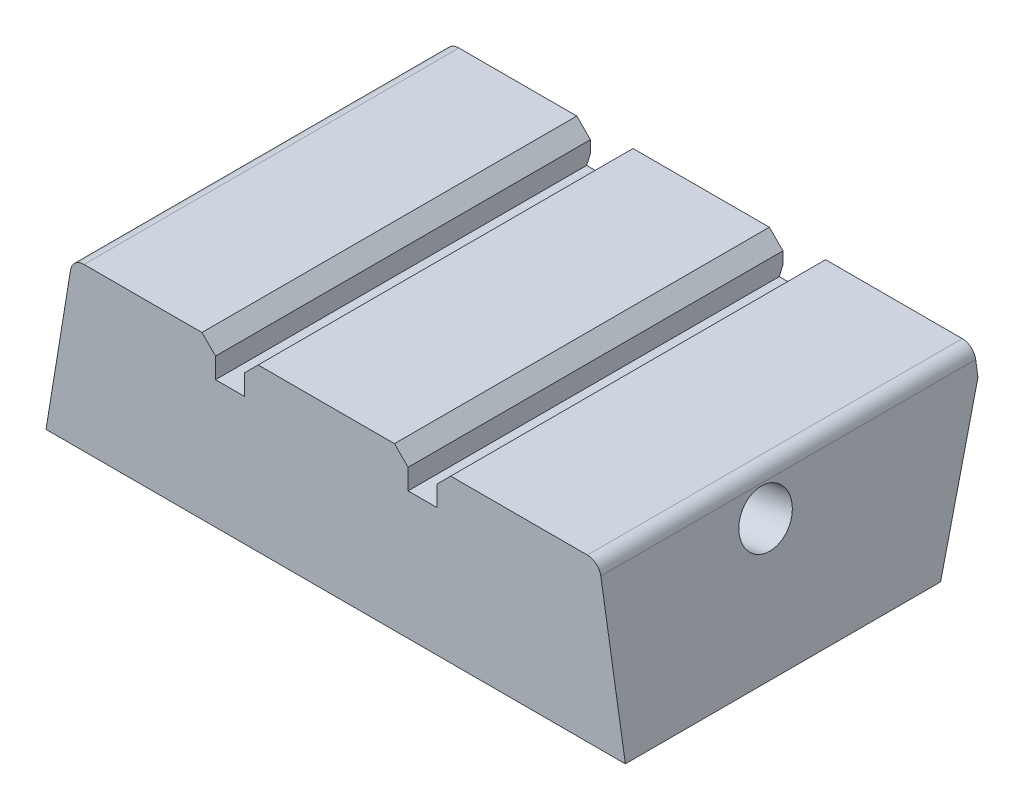
SolidWorks part; units mm, degrees
ref_plane "Front Plane" through (0, 0, 0) normal (0, 0, 1) x (1, 0, 0)
ref_plane "Top Plane" through (0, 0, 0) normal (0, 1, 0) x (1, 0, 0)
ref_plane "Right Plane" through (0, 0, 0) normal (1, 0, 0) x (0, 0, -1)
sketch "Sketch1" plane through (0, 0, 0) normal (0, 0, 1) x (1, 0, 0)
  line L0 (-17, -4.75) -> (-15.45, 4.75)
  line L1 (-17, -4.75) -> (17, -4.75)
  line L2 (-17, -4.75) -> (-17, 4.75)
  line L3 (-17, 4.75) -> (17, 4.75)
  line L4 (17, -4.75) -> (17, 4.75)
  line L5 (-17, -4.75) -> (17, 4.75) construction
  line L6 (-17, 4.75) -> (17, -4.75) construction
  line L7 (17, -4.75) -> (15.45, 4.75)
  line L8 (-7.05, 4.75) -> (-7.05, 2.75)
  line L9 (-7.05, 2.75) -> (-5.35, 2.75)
  line L10 (-5.35, 2.75) -> (-5.35, 4.75)
  line L11 (4.25, 4.75) -> (4.25, 2.75)
  line L12 (4.25, 2.75) -> (5.95, 2.75)
  line L13 (5.95, 2.75) -> (5.95, 4.75)
  point P0 (0, 0)
  dimension "D1" = 30.9
  dimension "D2" = 34
  dimension "D3" = 9.5
  dimension "D4" = 1.7
  dimension "D5" = 8.4
  dimension "D6" = 9.6
  dimension "D7" = 9.5
  dimension "D8" = 2
extrude "Boss-Extrude1" add sketch "Sketch1" along normal blind 22 contours L13 L12 L11 L3 L10 L9 L8 L0 L1 L7 region at (0.0124, -0.1619, 0)
sketch "Sketch2" plane through (0, -4.75, 0) normal (0, -1, 0) x (1, 0, 0)
  line L0 (0, 6.7) -> (0, 11.35) construction
  line L1 (-5, -6.7) -> (5, -6.7)
  line L2 (-5, -6.7) -> (-5, 6.7)
  line L3 (-5, 6.7) -> (5, 6.7)
  line L4 (5, -6.7) -> (5, 6.7)
  line L5 (-5, -6.7) -> (5, 6.7) construction
  line L6 (-5, 6.7) -> (5, -6.7) construction
  line L7 (-5.85, 11.35) -> (5.85, 11.35) construction
  line L8 (-5.85, 16) -> (5.85, 16)
  line L9 (-5.85, 6.7) -> (5.85, 6.7)
  line L10 (-17, 0) -> (17, 0) construction
  arc A0 (-5.85, 16) -> (-5.85, 6.7) centre (-5.85, 11.35) ccw
  arc A1 (5.85, 6.7) -> (5.85, 16) centre (5.85, 11.35) ccw
  point P0 (0, 0)
  point P10 (0, 11.35)
  point P17 (7.6836, 6.9018)
  line M9 (-17, 0) -> (17, 0)
  dimension "D4" = 21
  dimension "D1" = 10
  dimension "D2" = 6.7
  dimension "D3" = 16
extrude "Cut-Extrude1" cut sketch "Sketch2" against normal blind 4.6 contours L9 A1 L8 A0 L3 | L4 L3 L2 M9 region at (0, -4.75, 3.35) region at (0, -4.75, 11.35)
extrude "Cut-Extrude2" cut sketch "Sketch2<3>" against normal blind 6.5 contours L4 L3 L2 M9 region at (0, -4.75, 3.35)
sketch "Sketch2<3>" plane through (0, -4.75, 0) normal (0, -1, 0) x (1, 0, 0) same geometry as "Sketch2"
sketch "Sketch3" plane through (0, -0.15, 0) normal (0, -1, 0) x (1, 0, 0)
  line L0 (-10.5, 11.35) -> (10.5, 11.35) construction
  line L1 (-7.25, 11.35) -> (0, 0) construction
  line L2 (0, 0) -> (7.25, 11.35) construction
  arc A0 (-5.85, 16) -> (-5.85, 6.7) centre (-5.85, 11.35) ccw construction
  arc A1 (5.85, 6.7) -> (5.85, 16) centre (5.85, 11.35) ccw construction
  circle A2 centre (-7.25, 11.35) radius 0.95
  circle A3 centre (7.25, 11.35) radius 0.95
  dimension "D1" = 14.5
  dimension "D2" = 1.9
extrude "Cut-Extrude3" cut sketch "Sketch3" against normal blind 2.5
sketch "Sketch4" plane through (0, -0.15, 0) normal (0, -1, 0) x (1, 0, 0)
  line L0 (-6.1487, 9.7408) -> (-8.9115, 7.85)
  line L1 (-6.1487, 12.9592) -> (-8.9115, 14.85)
  line L2 (6.1487, 12.9592) -> (8.9115, 14.85)
  line L3 (6.1487, 9.7408) -> (8.9115, 7.85)
  circle A0 centre (-7.25, 11.35) radius 0.95 construction
  circle A1 centre (-7.25, 11.35) radius 0.95
  circle A2 centre (7.25, 11.35) radius 0.95 construction
  circle A3 centre (7.25, 11.35) radius 0.95
  circle A4 centre (-7.25, 11.35) radius 1.95
  circle A5 centre (7.25, 11.35) radius 1.95
  arc A6 (-5.85, 16) -> (-5.85, 6.7) centre (-5.85, 11.35) ccw construction
  arc A7 (-5.85, 16) -> (-5.85, 6.7) centre (-5.85, 11.35) ccw
  arc A8 (5.85, 6.7) -> (5.85, 16) centre (5.85, 11.35) ccw construction
  arc A9 (5.85, 6.7) -> (5.85, 16) centre (5.85, 11.35) ccw
  point P24 (-8.8137, 14.9331)
  circle M9 centre (-7.25, 11.35) radius 0.95
  circle M10 centre (7.25, 11.35) radius 0.95
  arc M14 (5.85, 6.7) -> (5.85, 16) centre (5.85, 11.35) ccw
  arc M16 (-5.85, 16) -> (-5.85, 6.7) centre (-5.85, 11.35) ccw
  dimension "D3" = 7
  dimension "D1" = 1
  dimension "D2" = 1
extrude "Boss-Extrude2" add sketch "Sketch4" along normal offset from surface (2.1 mm away) 2.5 contours A4 L1 L0 M16 | A4 M9 | A5 L3 L2 M14 | A5 M10 region at (-7.5766, -0.15, 8.8634) region at (-9.1448, -0.15, 11.35) region at (7.5766, -0.15, 13.8366) region at (8.1339, -0.15, 13.026) up to face at (0, -4.75, 8.5667)
sketch "Sketch5" plane through (15.8043, 2.5786, 0) normal (0.9869, 0.161, 0) x (0, 0, -1)
  line L0 (0, -7.4255) -> (0, 2.2001) construction
  line L1 (-22, 2.2001) -> (0, 2.2001) construction
  circle A0 centre (-12.6, -0.1499) radius 1.55
  dimension "D1" = 12.6
  dimension "D3" = 3.1
  dimension "D2" = 0.8
extrude "Cut-Extrude4" cut sketch "Sketch5" against normal blind 7
sketch "Sketch6" plane through (-15.8043, 2.5786, 0) normal (-0.9869, 0.161, 0) x (0, 0, 1)
  line L0 (12.6, 4.9478) -> (12.6, -0.1499) construction
  line L1 (22, 2.2001) -> (0, 2.2001) construction
  circle A0 centre (12.6, -0.1499) radius 1.55
  ellipse E0 centre (12.6, 4.9478) end of major axis (14.15, 4.9478) minor radius 1.4696 construction
  ellipse E1 centre (12.6, 4.9478) end of major axis (14.15, 4.9478) minor radius 1.4696 construction
  dimension "D1" = 0.8
  dimension "D2" = 3.1
extrude "Cut-Extrude5" cut sketch "Sketch6" against normal blind 7
sketch "Sketch7" plane through (0, 0, 0) normal (1, 0, 0) x (0, 0, -1)
  line L0 (0, 3.25) -> (-3.5, -4.75)
  line L1 (-3.5, -4.75) -> (1.4524, -4.75)
  line L2 (1.4524, -4.75) -> (0, 3.25)
  line L3 (-22, 4.75) -> (0, 4.75) construction
  line L4 (0, -4.75) -> (0, 4.75) construction
  line L5 (-22, -4.75) -> (0, -4.75) construction
  point P7 (-3.5, -4.75)
  point P10 (0, 3.25)
  dimension "D1" = 1.5
  dimension "D2" = 3.5
extrude "Cut-Extrude6" cut sketch "Sketch7" against normal through all both and the other way through all
fillet "Fillet1" radius 0.8 2 edges at (15.45, 4.75, 11) (-15.45, 4.75, 11)
chamfer "Chamfer1" distance 0.8 angle 45 4 edges at (5.95, 4.75, 11) (4.25, 4.75, 11) (-5.35, 4.75, 11) (-7.05, 4.75, 11)
chamfer "Chamfer2" distance 0.8 angle 45 7 edges at (5, -4.75, 5.1) (5.425, -4.75, 6.7) (10.5, -4.75, 11.35) (0, -4.75, 16) (-5.425, -4.75, 6.7) (-10.5, -4.75, 11.35) (-5, -4.75, 5.1)
chamfer "Chamfer3" distance 1.5 angle 45 1 edges at (0, -0.15, 6.7)
chamfer "Chamfer4" distance 0.5 angle 45 6 edges at (7.5301, -2.25, 8.7954) (5.3, -2.25, 11.35) (7.5301, -2.25, 13.9046) (-7.5301, -2.25, 8.7954) (-5.3, -2.25, 11.35) (-7.5301, -2.25, 13.9046)
